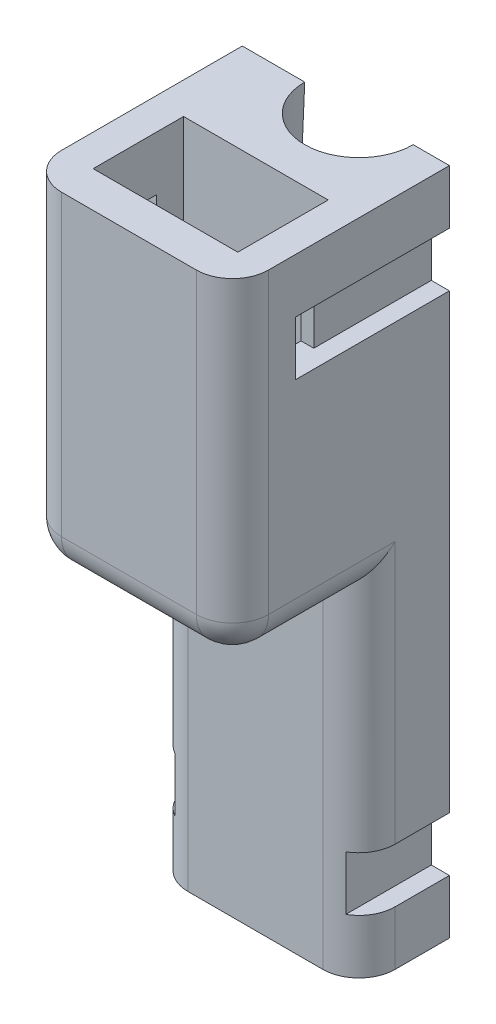
SolidWorks part; units mm, degrees
note: The reader was unsure of these and kept them because the rebuilt part matched: shared geometry of "Croquis2<4>".
ref_plane "Alzado" through (0, 0, 0) normal (0, 0, 1) x (1, 0, 0)
ref_plane "Planta" through (0, 0, 0) normal (0, 1, 0) x (1, 0, 0)
ref_plane "Vista lateral" through (0, 0, 0) normal (1, 0, 0) x (0, 0, -1)
sketch "Croquis1" plane through (0, 0, 0) normal (0, 0, 1) x (1, 0, 0)
  line L0 (0, 7) -> (0, -7)
  line L1 (0, -7) -> (0, -10)
  line L2 (0, 0) -> (-3.5, 0) construction
  line L3 (-3.5, 7) -> (-3.5, -7)
  line L4 (-3.5, -7) -> (-2.5, -9.6451)
  line L5 (-2.5, -9.6451) -> (-2.5, -18.6451)
  line L6 (-2.5, -18.6451) -> (-0.8, -18.6451)
  line L12 (0, 7) -> (0, 10)
  line L18 (-2.5, 18.6451) -> (-0.8, 18.6451)
  line L19 (-2.5, 9.6451) -> (-2.5, 18.6451)
  line L20 (-3.5, 7) -> (-2.5, 9.6451)
  dimension "D1" = 7
  dimension "D2" = 3
  dimension "D3" = 7
  dimension "D4" = 9
  dimension "D5" = 2.5
  dimension "D6" = 3.5
  dimension "D7" = 1.7
ref_plane "Plano1" through (0, 0, 0) normal (0, 0, 1) x (1, 0, 0)
sketch "Croquis2" plane through (0, 0, 0) normal (0, 0, 1) x (1, 0, 0)
  line L7 (0, -9.9421) -> (0, 27.0579)
  line L8 (0, 27.0579) -> (-3, 27.0579)
  line L9 (-6.4535, 27.0579) -> (5, 27.0579)
  line L10 (-6.4535, 27.0579) -> (-6.4535, -9.9421)
  line L11 (-6.4535, -9.9421) -> (5, -9.9421)
  line L12 (5, 27.0579) -> (5, -9.9421)
  line L13 (0, -9.9421) -> (-3, -9.9421)
  line L14 (0, 8.5579) -> (-4, 8.5579) construction
  arc A0 (-3, -9.9421) -> (-3, 27.0579) centre (363.9948, 8.5579) cw
  point P3 (0, -10.1098)
  point P6 (-3, -9.9421)
  point P7 (0, 27.0579)
  dimension "D1" = 5
  dimension "D2" = 11.4535
  dimension "D3" = 3
  dimension "D4" = 4
  dimension "D5" = 37
  dimension "D6" = 3
extrude "Saliente-Extruir1" add sketch "Croquis2" along normal blind 5 contours L12 L11 L10 L9
revolve "Cortar-Revolución1" cut sketch "Croquis2<4>" angle 360 about L7
sketch "Croquis2<4>" plane through (0, 0, 0) normal (0, 0, 1) x (1, 0, 0) same geometry as "Croquis2"
sketch "Croquis3" plane through (0, 0, 0) normal (0, 0, -1) x (-1, 0, 0)
  line L0 (0, 0.5579) -> (0, 16.5579)
  line L1 (0, 7) -> (0, -7) construction
  line L6 (12, 6.5579) -> (12, 10.5579)
  line L7 (0, 8.5579) -> (12, 8.5579) construction
  line L8 (6.4535, -9.9421) -> (3, -9.9421) construction
  line L9 (6.4535, 27.0579) -> (6.4535, -9.9421) construction
  arc A0 (12, 10.5579) -> (0, 16.5579) centre (16.0742, 33.7062) cw
  arc A1 (12, 6.5579) -> (0, 0.5579) centre (16.0742, -16.5905) ccw
  point P11 (0, 0)
  point P12 (0, 0)
  point P13 (0, 0)
  point P17 (6.4535, 8.5579)
  dimension "D1" = 8
  dimension "D2" = 12
  dimension "D3" = 2
sketch "Croquis6" plane through (0, 0, 5) normal (0, 0, 1) x (1, 0, 0)
  line L0 (5, 27.0579) -> (5, -9.9421) construction
  line L1 (5, 8.5579) -> (-6.4535, 8.5579)
  line L2 (5, 8.5579) -> (5, 27.0579)
  line L3 (5, 27.0579) -> (-6.4535, 27.0579)
  line L4 (-6.4535, 8.5579) -> (-6.4535, 27.0579)
extrude "Saliente-Extruir2" add sketch "Croquis6" along normal blind 7
sketch "Croquis4" plane through (0, 0, 0) normal (0, 0, -1) x (-1, 0, 0)
  line L0 (-5, 27.0579) -> (-5, -9.9421) construction
  line L1 (-5, 24.0579) -> (-4, 24.0579)
  line L2 (-5, 24.0579) -> (-5, 21.0579)
  line L3 (-5, 21.0579) -> (-4, 21.0579)
  line L4 (-4, 24.0579) -> (-4, 21.0579)
  line L5 (-3, 27.0579) -> (-5, 27.0579) construction
  line L6 (5.4535, 24.0579) -> (6.4535, 24.0579)
  line L7 (5.4535, 24.0579) -> (5.4535, 21.0579)
  line L8 (5.4535, 21.0579) -> (6.4535, 21.0579)
  line L9 (6.4535, 24.0579) -> (6.4535, 21.0579)
  line L10 (5.4535, -3.9421) -> (6.4535, -3.9421)
  line L11 (5.4535, -3.9421) -> (5.4535, -6.9421)
  line L12 (5.4535, -6.9421) -> (6.4535, -6.9421)
  line L13 (6.4535, -3.9421) -> (6.4535, -6.9421)
  line L14 (-5, -3.9421) -> (-4, -3.9421)
  line L15 (-5, -3.9421) -> (-5, -6.9421)
  line L16 (-5, -6.9421) -> (-4, -6.9421)
  line L17 (-4, -3.9421) -> (-4, -6.9421)
  line L18 (-3, -9.9421) -> (-5, -9.9421) construction
  line L19 (6.4535, 27.0579) -> (6.4535, -9.9421) construction
  dimension "D1" = 1
  dimension "D2" = 3
  dimension "D3" = 3
  dimension "D6" = 3
  dimension "D7" = 0
  dimension "D4" = 2
  dimension "D5" = 2
extrude "Cortar-Extruir2" cut sketch "Croquis4" against normal blind 6.5
sketch "Croquis5" plane through (4, 0, 0) normal (1, 0, 0) x (0, 0, -1)
  line L0 (-6.5, 24.0579) -> (0, 24.0579) construction
  line L1 (-8.5, 21.0579) -> (-6.5, 21.0579)
  line L2 (-8.5, 21.0579) -> (-8.5, 24.0579)
  line L3 (-8.5, 24.0579) -> (-6.5, 24.0579)
  line L4 (-6.5, 21.0579) -> (-6.5, 24.0579)
  line L5 (-5, -6.9421) -> (-5, -3.9421) construction
  line L6 (-7.9583, -12.6451) -> (-7.9583, -15.6451)
  line L7 (-4, -15.6451) -> (-7.9583, -15.6451)
  line L8 (-4, -12.6451) -> (-4, -15.6451)
  line L9 (-4, -12.6451) -> (-7.9583, -12.6451)
  line L10 (0, 21.0579) -> (0, 24.0579) construction
  point P4 (-6.5, 20.8826)
  point P9 (-6.5, 21.0579)
  dimension "D1" = 2
  dimension "D2" = 6.5
  dimension "D3" = 1
extrude "Cortar-Extruir3" cut sketch "Croquis5" against normal up to vertex and the other way up to vertex
sketch "Croquis7" plane through (0, 27.0579, 0) normal (0, 1, 0) x (1, 0, 0)
  line L0 (5, -12) -> (-6.4535, -12) construction
  line L1 (3.2965, -10) -> (-4.7035, -10)
  line L2 (3.2965, -10) -> (3.2965, -5)
  line L3 (3.2965, -5) -> (-4.7035, -5)
  line L4 (-4.7035, -10) -> (-4.7035, -5)
  line L5 (-6.4535, -12) -> (-6.4535, 0) construction
  dimension "D1" = 8
  dimension "D2" = 5
  dimension "D3" = 2
  dimension "D4" = 1.75
extrude "Cortar-Extruir4" cut sketch "Croquis7" against normal blind 15
fillet "Redondeo1" radius 2 7 edges at (5, 8.5579, 8.5) (-6.4535, 8.5579, 8.5) (-0.7268, 8.5579, 12) (5, 17.8079, 12) (-6.4535, 17.8079, 12) (-6.4535, -8.4421, 5) (5, 2.3079, 5)
extrude "Cortar-Extruir5" cut sketch "Croquis3" against normal blind 3
